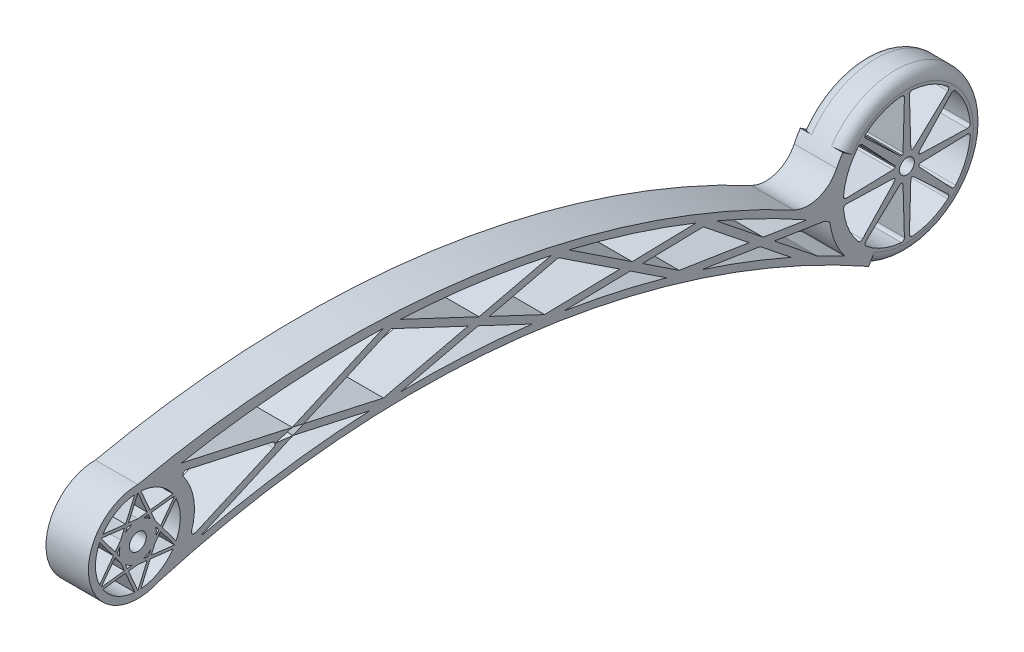
SolidWorks part; units mm, degrees
material "ABS"
ref_plane "Płaszczyzna przednia" through (0, 0, 0) normal (0, 0, 1) x (1, 0, 0)
ref_plane "Płaszczyzna górna" through (0, 0, 0) normal (0, 1, 0) x (1, 0, 0)
ref_plane "Płaszczyzna prawa" through (0, 0, 0) normal (1, 0, 0) x (0, 0, -1)
sketch "Szkic1" plane through (0, 0, 0) normal (1, 0, 0) x (0, 0, -1)
  line L11 (54.596, 25.632) -> (86.712, 39.8517)
  line L12 (58.7146, 24.7214) -> (86.848, 18.5017)
  line L13 (21.9483, 8.4427) -> (54.8577, 23.0137)
  line L14 (14.2088, 32.0004) -> (50.7391, 23.9243)
  line L15 (18.133, 9.4875) -> (50.7391, 23.9243)
  line L16 (15.3713, 34.3038) -> (54.596, 25.632)
  line L17 (58.7146, 24.7214) -> (89.5507, 38.3745)
  line L18 (54.8577, 23.0137) -> (81.9946, 17.0143)
  line L19 (124.3011, 24.762) -> (143.8506, 15.5491)
  line L20 (120.668, 26.4741) -> (146.1803, 32.488)
  line L21 (120.3919, 23.8405) -> (139.5065, 14.8326)
  line L22 (124.3011, 24.762) -> (148.7435, 30.5237)
  line L23 (89.5507, 38.3745) -> (116.7588, 25.5526)
  line L24 (150.7937, 13.2107) -> (174.1254, 13.7558)
  line L25 (200.0076, 14.3606) -> (216.1837, 1.3959)
  line L26 (92.9665, 17.3755) -> (120.3919, 23.8405)
  line L27 (148.7435, 30.5237) -> (170.4693, 16.1711)
  line L28 (199.4355, 1.51) -> (220.1167, -1.7563)
  line L29 (92.8118, 39.6014) -> (120.668, 26.4741)
  line L30 (143.8506, 15.5491) -> (170.4693, 16.1711)
  line L31 (204.6, 13.8838) -> (221.1623, 0.6096)
  line L32 (86.848, 18.5017) -> (116.7588, 25.5526)
  line L33 (152.4856, 31.0479) -> (174.8499, 16.2734)
  line L34 (191.4595, 5.3007) -> (216.1837, 1.3959)
  line L35 (174.1254, 13.7558) -> (186.9931, 5.255)
  line L36 (174.8499, 16.2734) -> (197.5033, 16.8027)
  line L37 (178.5059, 13.8582) -> (191.4595, 5.3007)
  line L38 (178.5059, 13.8582) -> (200.0076, 14.3606)
  line L39 (221.1623, 0.6096) -> (236.6131, -1.8307)
  line L40 (220.1167, -1.7563) -> (231.0391, -10.5102)
  line L41 (225.0952, -2.5426) -> (240.3985, -14.8077)
  line L42 (225.0952, -2.5426) -> (242.6899, -5.3214)
  circle A0 centre (0, 17.9252) radius 17.5
  circle A1 centre (0, 17.9252) radius 3
  arc A2 (244.5117, -3.4071) -> (0, 35.4252) centre (72.3468, -298.2483) ccw
  arc A3 (236.7304, -15.8386) -> (7.1155, 1.9371) centre (98.3142, -311.9128) ccw construction
  circle A4 centre (272.0097, -3.0749) radius 27.5
  arc A5 (244.7278, -6.5311) -> (8.876, 33.0072) centre (76.3157, -287.9196) ccw
  arc A6 (258.529, -27.0441) -> (7.1155, 1.9371) centre (98.3142, -311.9128) ccw
  arc A7 (250.0383, -19.613) -> (12.9603, 6.166) centre (98.3142, -311.9128) ccw
  arc A8 (16.8751, 7.1907) -> (12.2878, 33.7053) centre (0, 17.9252) ccw
  arc A9 (237.7892, -13.5739) -> (6.4179, 4.3378) centre (98.3142, -311.9128) ccw construction
  arc A10 (231.9153, 3.596) -> (247.1439, 8.6699) centre (237.1044, 13.4118) ccw
  circle A11 centre (0, 17.9252) radius 20 construction
  point P3 (206.3115, -91.4332)
  point P7 (210.9875, -66.8744)
  point P10 (222.3945, 17.8256)
  point P11 (200.4339, 25.8186)
  point P12 (188.4632, -7.0706)
  point P21 (193.8769, -58.5267)
  point P22 (187.3305, -92.9091)
  point P23 (210.2881, -97.2801)
  point P24 (216.8345, -62.8978)
  point P27 (210.4238, -15.0636)
  point P30 (207.4354, -8.655)
  point P31 (215.9859, 14.8373)
  point P43 (20, 17.9252)
  point P50 (242.3808, -10.2063)
  dimension "D5" = 327.9362
  dimension "D2" = 2.5
  dimension "D7" = 2.5
  dimension "D9" = 6
  dimension "D10" = 35
  dimension "D17" = 72.3468
  dimension "D3" = 341.4265
  dimension "D4" = 55
  dimension "D6" = 326.8317
  dimension "D15" = 8.876
  dimension "D12" = 7.1155
  dimension "D14" = 98.3142
  dimension "D16" = 12.2878
  dimension "D18" = 1.9371
  dimension "D22" = 242.3808
extrude "Dodanie-wyciągnięcie1" add sketch "Szkic1" along normal blind 15 contours A5 A2 A0 | A7 A0 A6 | A5 L39 L31 L36 L33 L20 L29 L11 L16 A8 L14 L15 A7 L13 L18 L26 L21 L24 L35 L28 L40 L41 L42 L32 L12 L17 L23 L30 L19 L22 L27 L37 L38 L25 L34 | A0 A1 | A8 A5 A0 A7 | A2 | A6 | A4 region at (0, 30.5766, -71.6127) region at (0, 41.5191, -50.6962) region at (0, 32.6615, -13.0786) region at (0, 26.3663, -14.7621) region at (0, 6.4374, -14.9808) region at (0, 1.305, -241.7606) region at (0, -3.0749, -272.0097)
sketch "Szkic2" plane through (15, 0, 0) normal (1, 0, 0) x (0, 0, -1)
  line L0 (-8.0458, 18.7641) -> (-6.0679, 21.4286)
  line L1 (-7.4231, 17.9252) -> (-6.356, 19.3628)
  line L2 (-7.4231, 17.9252) -> (-6.356, 16.4877)
  line L3 (-12.9904, 10.4252) -> (-5.1962, 20.9252) construction
  line L4 (-8.0458, 17.0864) -> (-6.0679, 14.4219)
  line L5 (-12.9904, 25.4252) -> (-5.1962, 14.9252) construction
  line L6 (0, 32.9252) -> (-3.2964, 25.3125)
  line L7 (0, 32.9252) -> (3.2964, 25.3125)
  line L8 (12.9904, 25.4252) -> (4.7494, 24.4736)
  line L9 (12.9904, 25.4252) -> (8.0458, 18.7641)
  line L10 (12.9904, 10.4252) -> (8.0458, 17.0864)
  line L11 (12.9904, 10.4252) -> (4.7494, 11.3768)
  line L12 (0, 2.9252) -> (3.2964, 10.5379)
  line L13 (0, 2.9252) -> (-3.2964, 10.5379)
  line L14 (-12.9904, 10.4252) -> (-4.7494, 11.3768)
  line L15 (-12.9904, 10.4252) -> (-8.0458, 17.0864)
  line L16 (-12.9904, 25.4252) -> (-8.0458, 18.7641)
  line L17 (-12.9904, 25.4252) -> (-4.7494, 24.4736)
  line L18 (0, 35.4418) -> (0.0072, 35.4252)
  line L19 (0, 35.4418) -> (-0.0072, 35.4252)
  line L20 (-15.1698, 9.1669) -> (-15.159, 9.1815)
  line L21 (-15.1698, 9.1669) -> (-15.1518, 9.169)
  line L22 (-4.7494, 24.4736) -> (-6.0679, 21.4286)
  line L23 (-3.2964, 25.3125) -> (0, 24.9319)
  line L24 (-3.7115, 24.3538) -> (-1.933, 24.1484)
  line L25 (-3.7115, 24.3538) -> (-4.4229, 22.7109)
  line L26 (-12.9904, 25.4252) -> (0, 23.9252) construction
  line L27 (3.7115, 24.3538) -> (4.4229, 22.7109)
  line L28 (-3.7115, 11.4967) -> (-1.933, 11.702)
  line L29 (-1.1075, 2.9662) -> (-4.3342, 10.4181)
  line L30 (-15.1698, 26.6835) -> (-15.159, 26.669)
  line L31 (-15.1698, 26.6835) -> (-15.1518, 26.6815)
  line L32 (1.1075, 2.9662) -> (4.3342, 10.4181)
  line L33 (0, 32.9252) -> (-5.1962, 20.9252) construction
  line L34 (-4.7494, 11.3768) -> (-6.0679, 14.4219)
  line L35 (-12.9904, 10.4252) -> (0, 11.9252) construction
  line L36 (15.1698, 9.1669) -> (15.159, 9.1815)
  line L37 (15.1698, 9.1669) -> (15.1518, 9.169)
  line L38 (15.1698, 26.6835) -> (15.159, 26.669)
  line L39 (15.1698, 26.6835) -> (15.1518, 26.6815)
  line L40 (7.4231, 17.9252) -> (6.356, 16.4877)
  line L41 (3.2964, 25.3125) -> (0, 24.9319)
  line L42 (-13.5087, 24.4457) -> (-8.6685, 17.9252)
  line L43 (-12.4012, 26.3638) -> (-4.3342, 25.4323)
  line L44 (-15.1698, 26.6835) -> (-6.0679, 14.4219) construction
  line L45 (-1.1075, 32.8843) -> (-4.3342, 25.4323)
  line L46 (-15.1698, 26.6835) -> (0.1147, 24.9186) construction
  line L47 (1.1075, 32.8843) -> (4.3342, 25.4323)
  line L48 (0, 35.4418) -> (-6.0679, 21.4286) construction
  line L49 (12.4012, 26.3638) -> (4.3342, 25.4323)
  line L50 (0, 35.4418) -> (6.1138, 21.3226) construction
  line L51 (13.5087, 24.4457) -> (8.6685, 17.9252)
  line L52 (15.1698, 26.6835) -> (-0.1147, 24.9186) construction
  line L53 (13.5087, 11.4048) -> (8.6685, 17.9252)
  line L54 (15.1698, 26.6835) -> (5.9991, 14.3292) construction
  line L55 (12.4012, 9.4866) -> (4.3342, 10.4181)
  line L56 (15.1698, 9.1669) -> (5.9991, 21.5213) construction
  line L57 (-12.4012, 9.4866) -> (-4.3342, 10.4181)
  line L58 (15.1698, 9.1669) -> (-0.1147, 10.9318) construction
  line L59 (-0.9177, 2.5279) -> (-6.0679, 14.4219) construction
  line L60 (-13.5087, 11.4048) -> (-8.6685, 17.9252)
  line L61 (-15.1698, 9.1669) -> (0.1147, 10.9318) construction
  line L62 (-3.7115, 11.4967) -> (-4.4229, 13.1396)
  line L63 (-15.1698, 9.1669) -> (-6.0679, 21.4286) construction
  line L64 (0.9177, 2.5279) -> (6.1138, 14.5279) construction
  line L65 (-3.2964, 10.5379) -> (0, 10.9186)
  line L66 (0, 32.9252) -> (5.1962, 20.9252) construction
  line L67 (8.0458, 18.7641) -> (6.0679, 21.4286)
  line L68 (12.9904, 25.4252) -> (5.1962, 14.9252) construction
  line L69 (4.7494, 24.4736) -> (6.0679, 21.4286)
  line L70 (0, 2.9252) -> (-5.1962, 14.9252) construction
  line L71 (3.7115, 11.4967) -> (4.4229, 13.1396)
  line L72 (3.7115, 24.3538) -> (1.933, 24.1484)
  line L73 (8.0458, 17.0864) -> (6.0679, 14.4219)
  line L74 (3.7115, 11.4967) -> (1.933, 11.702)
  line L75 (0, 2.9252) -> (5.1962, 14.9252) construction
  line L76 (12.9904, 25.4252) -> (0, 23.9252) construction
  line L77 (3.2964, 10.5379) -> (0, 10.9186)
  line L78 (7.4231, 17.9252) -> (6.356, 19.3628)
  line L79 (12.9904, 10.4252) -> (0, 11.9252) construction
  line L80 (12.9904, 10.4252) -> (5.1962, 20.9252) construction
  line L81 (4.7494, 11.3768) -> (6.0679, 14.4219)
  line L82 (-6.0679, 21.4286) -> (-5.6435, 21.1835) construction
  circle A1 centre (0, 17.9252) radius 17.5
  circle A2 centre (0, 17.9252) radius 15
  circle A3 centre (0, 17.9252) radius 6.5165
  point P5 (-0.2017, 28.9866)
  point P6 (-0.2017, 28.9866)
  point P7 (6.1719, 28.9866)
  point P9 (-0.2017, 33.3602)
  point P31 (0.9177, 3.3226)
  point P33 (-4.3244, 15.4286)
  point P34 (-10.8109, 24.1669)
  point P36 (-0.1147, 22.9318)
  point P37 (0, 30.4086)
  point P38 (4.2785, 20.5279)
  point P39 (-4.3244, 20.4219)
  point P40 (-10.8109, 11.6835)
  point P41 (-0.1147, 12.9186)
  point P48 (10.8109, 11.6835)
  point P49 (4.3932, 20.3292)
  point P50 (0.1147, 12.9186)
  point P51 (-0.9177, 3.3226)
  point P52 (4.2785, 15.3226)
  point P59 (10.8109, 24.1669)
  point P60 (4.3932, 15.5213)
  point P61 (0.1147, 22.9318)
  dimension "D2" = 30
  dimension "D3" = 35
  dimension "D5" = 6
extrude "Wytnij-wyciągnięcie1" cut sketch "Szkic2" against normal blind 10 contours L22 L17 L16 L0 | L42 A2 L60 | A3 L1 L2 | A3 L24 L25 | A3 L27 L72 | A3 L40 L78 | A3 L74 L71 | A3 L62 L28 | L14 L34 L4 L15 | L41 L7 L6 L23 | L49 A2 L47 | L45 A2 L43 | L8 L69 L67 L9 | L53 A2 L51 | L81 L11 L10 L73 | L57 A2 L29 | L12 L77 L65 L13 | L32 A2 L55 region at (15, 22.8242, 8.4853) region at (15, 13.0262, 8.4853) region at (15, 8.1273, 0) region at (15, 13.0262, -8.4853) region at (15, 22.8242, -8.4853) region at (15, 27.7232, 0) region at (15, 28.7889, 6.2721) region at (15, 17.9252, 12.5443) region at (15, 28.7889, -6.2721) region at (15, 7.0616, 6.2721) region at (15, 17.9252, -12.5443) region at (15, 7.0616, -6.2721) region at (15, 17.9252, 6.785) region at (15, 23.8012, 3.3925) region at (15, 12.0492, 3.3925) region at (15, 23.8012, -3.3925) region at (15, 12.0492, -3.3925) region at (15, 17.9252, -6.785)
ref_axis "Oś1" through (15, -3.0749, -272.0097) along (-1, 0, 0)
ref_plane "Płaszczyzna1" through (0, -116.9596, -207.9591) normal (0, 0.4902, 0.8716) x (1, 0, 0)
sketch "Szkic3" plane through (0, -116.9596, -207.9591) normal (0, 0.4902, 0.8716) x (1, 0, 0)
  line L1 (15, 130.6607) -> (0, 130.6607)
  line L3 (11, 103.1607) -> (4, 103.1607)
  line L6 (15, 130.6607) -> (0, 130.6607) construction
  line L7 (0, 107.1607) -> (0, 103.1607)
  line L8 (0, 103.1607) -> (15, 103.1607)
  line L9 (15, 103.1607) -> (15, 107.1607)
  arc A0 (11, 103.1607) -> (15, 107.1607) centre (11, 107.1607) ccw
  arc A1 (4, 103.1607) -> (0, 107.1607) centre (4, 107.1607) cw
  dimension "D1" = 4
revolve "Wycięcie-obrót1" cut sketch "Szkic3" angle 265 about L1 region at (0.8935, -26.2653, -258.967) region at (14.1065, -26.2653, -258.967) reverse direction yes
sketch "Szkic4" plane through (0, 0, 0) normal (-1, 0, 0) x (0, 0, 1)
  line L0 (-272.0097, -3.0749) -> (-294.5097, -3.0749) construction
  line L1 (-294.4935, -3.9278) -> (-276.287, -4.4732)
  line L2 (-294.4935, -2.2221) -> (-276.287, -1.6766)
  line L3 (-288.5112, 12.2205) -> (-276.0229, -1.0392)
  line L4 (-287.3051, 13.4266) -> (-274.0455, 0.9383)
  line L5 (-272.8626, 19.4089) -> (-273.408, 1.2023)
  line L6 (-271.1569, 19.4089) -> (-270.6114, 1.2023)
  line L7 (-256.7143, 13.4266) -> (-269.974, 0.9383)
  line L8 (-255.5082, 12.2205) -> (-267.9965, -1.0392)
  line L9 (-249.5259, -2.2221) -> (-267.7325, -1.6766)
  line L10 (-249.5259, -3.9278) -> (-267.7325, -4.4732)
  line L11 (-255.5082, -18.3703) -> (-267.9965, -5.1107)
  line L12 (-256.7143, -19.5764) -> (-269.974, -7.0881)
  line L13 (-271.1569, -25.5587) -> (-270.6114, -7.3522)
  line L14 (-272.8626, -25.5587) -> (-273.408, -7.3522)
  line L15 (-287.3051, -19.5764) -> (-274.0455, -7.0881)
  line L16 (-288.5112, -18.3703) -> (-276.0229, -5.1107)
  circle A0 centre (-272.0097, -3.0749) radius 22.5
  circle A1 centre (-272.0097, -3.0749) radius 4.5
  circle A2 centre (-272.0097, -3.0749) radius 2.6413
  point P39 (-272.0097, -3.0749)
  dimension "D1" = 8
  dimension "D2" = 9
  dimension "D3" = 45
extrude "Wytnij-wyciągnięcie2" cut sketch "Szkic4" against normal through all contours A1 L15 A0 L14 | A1 L1 A0 L16 | A1 L3 A0 L2 | A1 L5 A0 L4 | A1 L7 A0 L6 | A1 L9 A0 L8 | A1 L11 A0 L10 | A1 L13 A0 L12 | A2 region at (0, -9.1776, -286.743) region at (0, 3.0278, -286.743) region at (0, -17.8082, -278.1124) region at (0, 11.6584, -278.1124) region at (0, -17.8082, -265.907) region at (0, 11.6584, -265.907) region at (0, -9.1776, -257.2764) region at (0, 3.0278, -257.2764) region at (0, -3.0749, -272.0097)
fillet "Zaokrąglenie2" radius 1 32 edges at (7.5, -1.0392, -267.9965) (7.5, -1.6766, -267.7325) (7.5, 12.2205, -255.5082) (7.5, -2.2221, -249.5259) (7.5, -7.0881, -269.974) (7.5, -7.3522, -270.6114) (7.5, -19.5764, -256.7143) (7.5, -4.4732, -267.7325) (7.5, -7.0881, -274.0455) (7.5, -7.3522, -273.408) (7.5, -3.9278, -249.5259) (7.5, -18.3703, -255.5082) (7.5, 19.4089, -272.8626) (7.5, -1.0392, -276.0229) (7.5, -4.4732, -276.287) (7.5, 12.2205, -288.5112) (7.5, -18.3703, -288.5112) (7.5, -25.5587, -272.8626) (7.5, -5.1107, -276.0229) (7.5, -1.6766, -276.287) (7.5, 0.9383, -274.0455) (7.5, 1.2023, -273.408) (7.5, -25.5587, -271.1569) (7.5, -19.5764, -287.3051) (7.5, 13.4266, -287.3051) (7.5, -2.2221, -294.4935) (7.5, -3.9278, -294.4935) (7.5, -5.1107, -267.9965) (7.5, 1.2023, -270.6114) (7.5, 0.9383, -269.974) (7.5, 19.4089, -271.1569) (7.5, 13.4266, -256.7143)
ref_axis "Oś2" through (15, -3.0749, -272.0097) along (-1, 0, 0)
fillet "Zaokrąglenie3" radius 1 3 edges at (7.5, 23.9243, -50.7391) (7.5, 32.0004, -14.2088) (7.5, 9.4875, -18.133)
ref_axis "Oś3" through (15, 17.9252, 0) along (-1, 0, 0)
